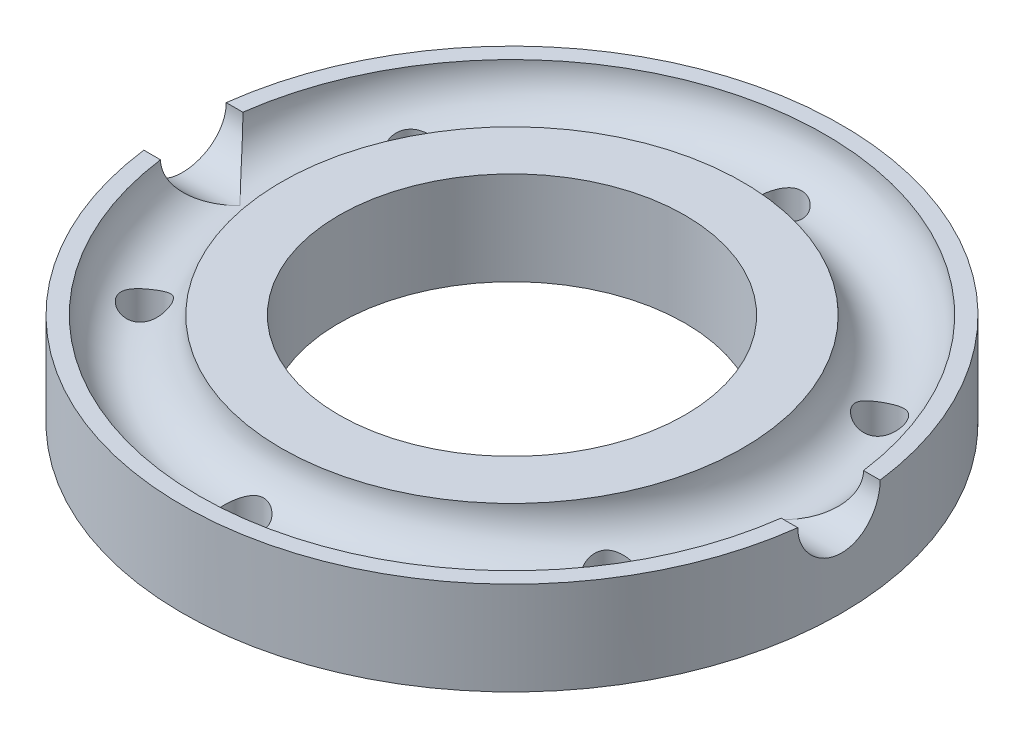
SolidWorks part; units mm, degrees
ref_plane "Front Plane" through (0, 0, 0) normal (0, 0, 1) x (1, 0, 0)
ref_plane "Top Plane" through (0, 0, 0) normal (0, 1, 0) x (1, 0, 0)
ref_plane "Right Plane" through (0, 0, 0) normal (1, 0, 0) x (0, 0, -1)
ref_axis "Centerline" through (0, 55, 0) along (0, -1, 0)
sketch "Sketch1" plane through (0, 0, 0) normal (0, 1, 0) x (1, 0, 0)
  circle A0 centre (0, 0) radius 10.414
  circle A1 centre (0, 0) radius 8.001
  dimension "D1" = 20.828
  dimension "D2" = 16.002
extrude "Boss-Extrude1" add sketch "Sketch1" along normal blind 4.318
sketch "Sketch2" plane through (0, 0, 0) normal (0, -1, 0) x (1, 0, 0)
  circle A0 centre (0, 0) radius 8.001
  circle A1 centre (0, 0) radius 15.24
  dimension "D1" = 30.48
  dimension "D2" = 16.002
extrude "Boss-Extrude2" add sketch "Sketch2" along normal blind 4.318
sketch "Sketch3" plane through (0, 0, 0) normal (0, 0, 1) x (1, 0, 0)
  line L0 (15.24, 0) -> (-15.24, 0) construction
  line L1 (10.668, 9.5598) -> (10.668, -10.185) construction
  circle A0 centre (12.573, 0) radius 1.905
  dimension "D2" = 3.81
  dimension "D1" = 10.668
revolve "Cut-Revolve1" cut sketch "Sketch3" angle 360 about axis through (0, 55, 0) along (0, -1, 0)
sketch "Sketch4" plane through (0, 0, 0) normal (0, 1, 0) x (1, 0, 0)
  circle A0 centre (0, 12.446) radius 0.9525
  point P2 (0, 0)
  dimension "D1" = 1.905
  dimension "D2" = 12.446
extrude "Cut-Extrude1" cut sketch "Sketch4" against normal up to next
pattern_circular "CirPattern1" count 6 over 360 about axis through (0, 55, 0) along (0, -1, 0) of "Cut-Extrude1"
sketch "Sketch5" plane through (0, 4.318, 0) normal (0, 1, 0) x (1, 0, 0)
  circle A0 centre (0, 0) radius 10.414
  dimension "D1" = 20.828
extrude "Cut-Extrude2" cut sketch "Sketch5" against normal blind 4.318
ref_plane "Inlet Plane" through (15.24, 0, 0) normal (1, 0, 0) x (0, 0, -1)
sketch "Sketch8" plane through (15.24, 0, 0) normal (1, 0, 0) x (0, 0, -1)
  circle A0 centre (0, 0) radius 1.905
  dimension "D1" = 3.81
extrude "Cut-Extrude3" cut sketch "Sketch8" against normal up to next
pattern_circular "CirPattern2" count 2 over 360 about axis through (0, 55, 0) along (0, -1, 0) of "Cut-Extrude3"
